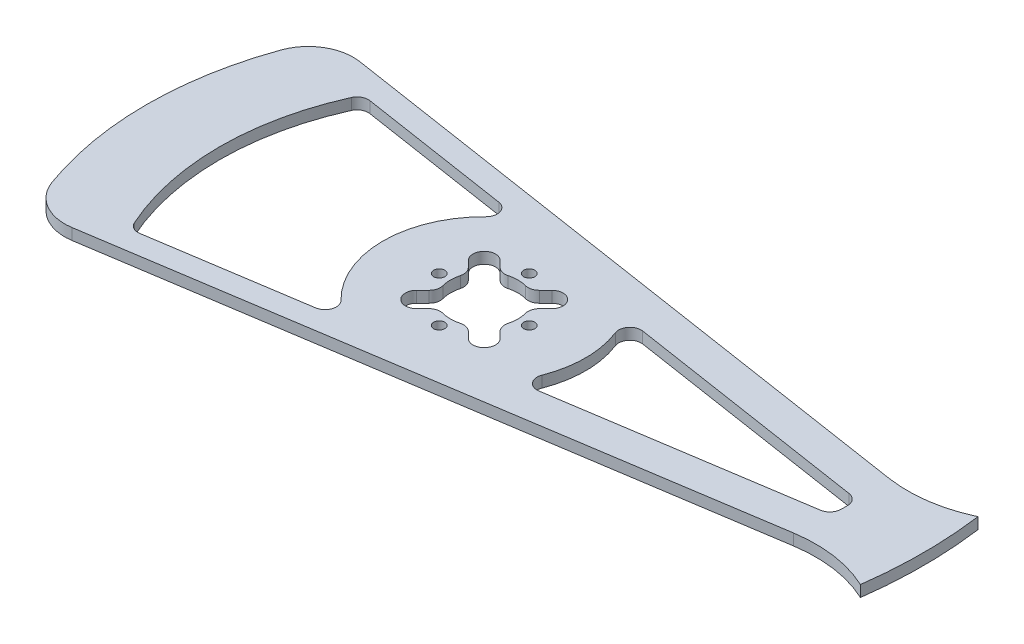
SolidWorks part; units mm, degrees
material "AISI 4340 Steel, normalized"
ref_plane "Front Plane" through (0, 0, 0) normal (0, 0, 1) x (1, 0, 0)
ref_plane "Top Plane" through (0, 0, 0) normal (0, 1, 0) x (1, 0, 0)
ref_plane "Right Plane" through (0, 0, 0) normal (1, 0, 0) x (0, 0, -1)
other "Center of Mass"
sketch "Sketch1" plane through (0, 0, 0) normal (0, 1, 0) x (1, 0, 0)
  line L0 (-170.9166, 84.1295) -> (201.4221, 26.8211)
  line L1 (-170.9166, -84.1295) -> (201.4221, -26.8211)
  line L2 (-134.097, 65.6129) -> (-28.7411, 49.3971)
  line L3 (-134.097, -65.6129) -> (-28.7411, -49.3971)
  line L4 (47.8972, 31.1766) -> (203.0691, 7.2933)
  line L5 (47.8972, -31.1766) -> (203.0691, -7.2933)
  line L6 (-23.5401, 14.5599) -> (-17.1901, 8.2099)
  line L7 (-19.05, -19.05) -> (19.05, -19.05) construction
  line L8 (-19.05, -19.05) -> (-19.05, 19.05) construction
  line L9 (-19.05, 19.05) -> (19.05, 19.05) construction
  line L10 (19.05, -19.05) -> (19.05, 19.05) construction
  line L11 (-19.05, -19.05) -> (19.05, 19.05) construction
  line L12 (-19.05, 19.05) -> (19.05, -19.05) construction
  line L13 (-14.5599, 23.5401) -> (-8.2099, 17.1901)
  line L14 (23.5401, 14.5599) -> (17.1901, 8.2099)
  line L15 (14.5599, 23.5401) -> (8.2099, 17.1901)
  line L16 (14.5599, -23.5401) -> (8.2099, -17.1901)
  line L17 (23.5401, -14.5599) -> (17.1901, -8.2099)
  line L18 (-23.5401, -14.5599) -> (-17.1901, -8.2099)
  line L19 (-14.5599, -23.5401) -> (-8.2099, -17.1901)
  line L20 (0, 0) -> (245.4188, 33.1679) construction
  circle A0 centre (0, 0) radius 57.15 construction
  circle A1 centre (0, 0) radius 247.65 construction
  arc A2 (245.4188, 33.1679) -> (245.4188, -33.1679) centre (0, 0) cw
  arc A3 (201.4221, -26.8211) -> (245.4188, -33.1679) centre (213.0139, -102.1343) cw
  arc A4 (201.4221, 26.8211) -> (245.4188, 33.1679) centre (213.0139, 102.1343) ccw
  circle A5 centre (0, 0) radius 190.5 construction
  arc A6 (-170.9166, 84.1295) -> (-170.9166, -84.1295) centre (0, 0) ccw
  circle A7 centre (0, 0) radius 203.2 construction
  circle A8 centre (0, 0) radius 149.2885 construction
  arc A9 (-134.097, 65.6129) -> (-134.097, -65.6129) centre (0, 0) ccw
  arc A10 (-28.7411, 49.3971) -> (-28.7411, -49.3971) centre (0, 0) ccw
  arc A11 (47.8972, 31.1766) -> (47.8972, -31.1766) centre (0, 0) cw
  arc A12 (203.0691, 7.2933) -> (203.0691, -7.2933) centre (0, 0) cw
  circle A13 centre (0, 0) radius 19.05
  circle A14 centre (-19.05, 19.05) radius 6.35
  circle A15 centre (19.05, 19.05) radius 6.35
  circle A16 centre (19.05, -19.05) radius 6.35
  circle A17 centre (-19.05, -19.05) radius 6.35
  point P18 (-190.5, 0)
  point P59 (0, 0)
  dimension "D1" = 495.3
  dimension "D2" = 44.45
  dimension "D3" = 17.5
  dimension "D4" = 114.3
  dimension "D5" = 57.15
  dimension "D6" = 76.2
  dimension "D12" = 38.1
  dimension "D14" = 12.7
  dimension "D15" = 4
  dimension "D7" = 12.7
  dimension "D8" = 12.7
  dimension "1.62" = 41.2115
  dimension "D10" = 19.05
  dimension "D11" = 19.05
  dimension "D13" = 38.1
extrude "Boss-Extrude1" add sketch "Sketch1" along normal blind 6.35 contours L0 A6 L1 A3 A2 A4 L2 A10 L3 A9 region at (14.5388, 0, -50.8365)
fillet "Fillet1" radius 6.35 8 edges at (47.8972, 3.175, 31.1766) (47.8972, 3.175, -31.1766) (203.0691, 3.175, -7.2933) (203.0691, 3.175, 7.2933) (-134.097, 3.175, -65.6129) (-134.097, 3.175, 65.6129) (-28.7411, 3.175, -49.3971) (-28.7411, 3.175, 49.3971)
fillet "Fillet2" radius 25.4 2 edges at (-170.9166, 3.175, -84.1295) (-170.9166, 3.175, 84.1295)
fillet "Fillet3" radius 6.35 8 edges at (-8.2099, 3.175, 17.1901) (8.2099, 3.175, 17.1901) (17.1901, 3.175, 8.2099) (17.1901, 3.175, -8.2099) (-8.2099, 3.175, -17.1901) (8.2099, 3.175, -17.1901) (-17.1901, 3.175, -8.2099) (-17.1901, 3.175, 8.2099)
sketch "Sketch2" plane through (0, 6.35, 0) normal (0, 1, 0) x (1, 0, 0)
  circle A0 centre (0, 25.4) radius 3.175
  arc A1 (4.9305, 18.4009) -> (-4.9305, 18.4009) centre (0, 0) ccw construction
  circle A2 centre (25.4, 0) radius 3.175
  circle A3 centre (0, -25.4) radius 3.175
  circle A4 centre (-25.4, 0) radius 3.175
  point P2 (0, 19.05)
  point P15 (0, 0)
  dimension "D1" = 6.35
  dimension "D2" = 6.35
  dimension "D3" = 4
extrude "Cut-Extrude1" cut sketch "Sketch2" against normal through all
